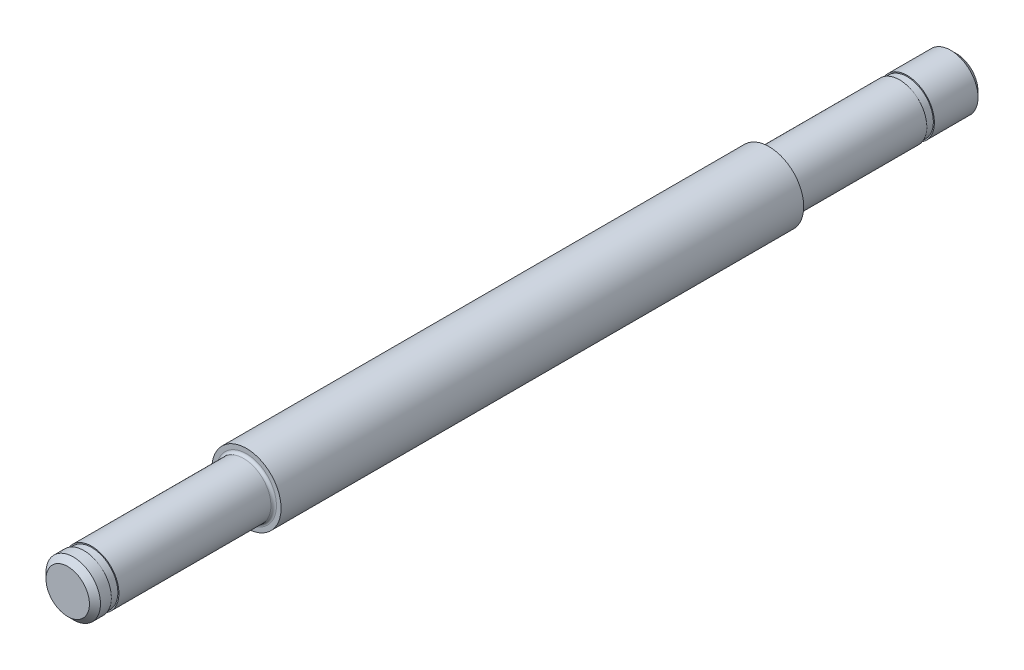
SolidWorks part; units mm, degrees
ref_plane "Front Plane" through (0, 0, 0) normal (0, 0, 1) x (1, 0, 0)
ref_plane "Top Plane" through (0, 0, 0) normal (0, 1, 0) x (1, 0, 0)
ref_plane "Right Plane" through (0, 0, 0) normal (1, 0, 0) x (0, 0, -1)
sketch "Sketch1" plane through (0, 0, 0) normal (0, 0, 1) x (1, 0, 0)
  circle A0 centre (0, 0) radius 2.5
  dimension "D1" = 5
extrude "Boss-Extrude1" add sketch "Sketch1" along normal mid plane 81.534
ref_axis "Axis1" through (0, 0, 40.767) along (0, 0, -1)
sketch "Sketch2" plane through (0, 0, 0) normal (1, 0, 0) x (0, 0, -1)
  line L0 (40.767, 2.5) -> (-40.767, 2.5) construction
  line L1 (-39.2646, 2.5) -> (-38.5646, 2.5)
  line L2 (-39.2646, 2.5) -> (-39.2646, 2.4)
  line L3 (-39.2646, 2.4) -> (-38.5646, 2.4)
  line L4 (-38.5646, 2.5) -> (-38.5646, 2.4)
  line L5 (-38.5646, -75.1766) -> (-38.5646, -68.8261) construction
  dimension "D1" = 0.1
  dimension "D2" = 0.7
revolve "Cut-Revolve1" cut sketch "Sketch2" angle 360 about axis through (0, 0, 40.767) along (0, 0, -1)
sketch "Sketch4" plane through (0, 0, -40.767) normal (0, 0, -1) x (-1, 0, 0)
  circle A0 centre (0, 0) radius 3.4022
extrude "Boss-Extrude2" [suppressed] add sketch "Sketch4" against normal up to surface (5.1753 mm away)
sketch "Sketch5" plane through (0, 0, 24.3646) normal (0, 0, -1) x (-1, 0, 0)
  circle A0 centre (0, 0) radius 3.175
  dimension "D1" = 6.35
extrude "Boss-Extrude3" add sketch "Sketch5" along normal blind 47.9552
ref_axis "Axis2" through (0, 0, -23.5906) along (0, 0, -1)
sketch "Sketch7" plane through (0, -92.7159, 0) normal (1, 0, 0) x (0, 0, 1)
  line L0 (-40.767, -95.2159) -> (-23.5906, -95.2159) construction
  line L1 (-36.262, -95.1159) -> (-35.562, -95.1159)
  line L2 (-36.262, -95.1159) -> (-36.262, -95.2159)
  line L3 (-36.262, -95.2159) -> (-35.562, -95.2159)
  line L4 (-35.562, -95.1159) -> (-35.562, -95.2159)
  dimension "D1" = 0.7
  dimension "D2" = 0.1
revolve "Cut-Revolve2" cut sketch "Sketch7" angle 360 about axis through (0, 0, -23.5906) along (0, 0, -1)
chamfer "Chamfer1" distance 0.508 angle 45 2 edges at (2.5, 0, 40.767) (2.5, 0, -40.767)
fillet "Fillet1" radius 0.254 2 edges at (-2.5, 0, -23.5906) (-2.5, 0, 24.3646)
